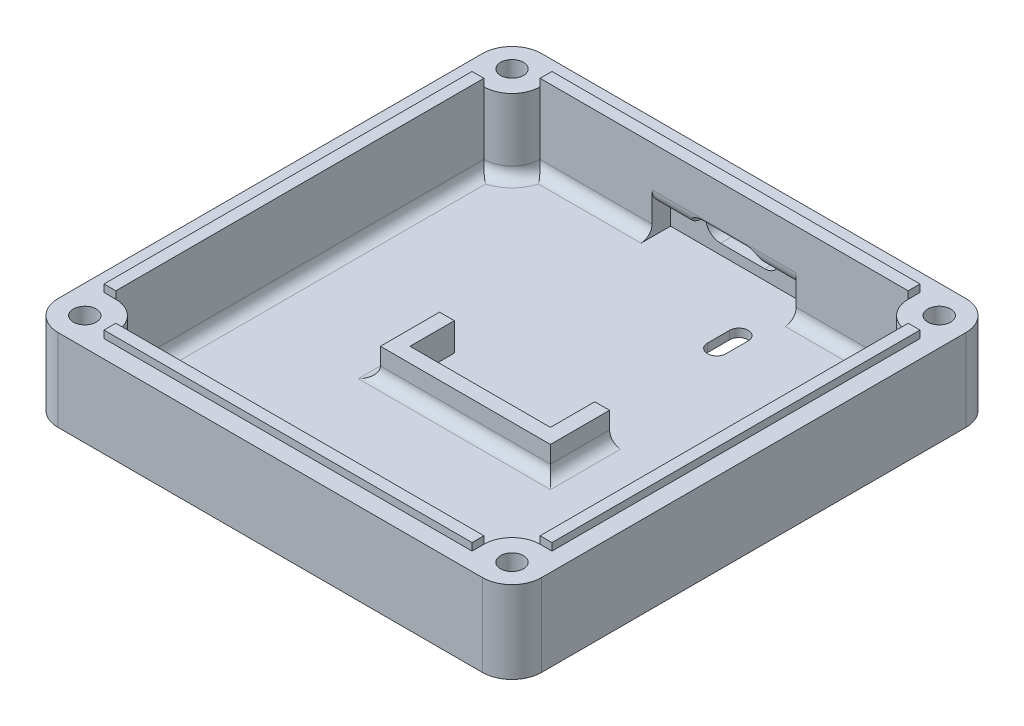
SolidWorks part; units mm, degrees
ref_plane "Front Plane" through (0, 0, 0) normal (0, 0, 1) x (1, 0, 0)
ref_plane "Top Plane" through (0, 0, 0) normal (0, 1, 0) x (1, 0, 0)
ref_plane "Right Plane" through (0, 0, 0) normal (1, 0, 0) x (0, 0, -1)
sketch "Sketch1" plane through (0, 0, 0) normal (0, 1, 0) x (1, 0, 0)
  line L1 (-32.7, -32.7) -> (32.7, -32.7)
  line L2 (-32.7, -32.7) -> (-32.7, 32.7)
  line L3 (-32.7, 32.7) -> (32.7, 32.7)
  line L4 (32.7, -32.7) -> (32.7, 32.7)
  line L5 (-32.7, -32.7) -> (32.7, 32.7) construction
  line L6 (-32.7, 32.7) -> (32.7, -32.7) construction
  point P0 (0, 0)
  dimension "D1" = 65.4
  dimension "D2" = 65.4
extrude "Boss-Extrude1" add sketch "Sketch1" along normal blind 1.12
fillet "Fillet1" radius 4 4 edges at (-32.7, 0.56, -32.7) (32.7, 0.56, -32.7) (32.7, 0.56, 32.7) (-32.7, 0.56, 32.7)
sketch "Sketch2" plane through (0, 1.12, 0) normal (0, 1, 0) x (1, 0, 0)
  line L0 (-32.7, 28.7) -> (-32.7, -28.7)
  line L1 (-28.7, -32.7) -> (28.7, -32.7)
  line L2 (32.7, -28.7) -> (32.7, 28.7)
  line L3 (28.7, 32.7) -> (-28.7, 32.7)
  line L4 (0, 0) -> (0, 28.7) construction
  line L11 (0, 0) -> (28.7, 0) construction
  line L12 (0, 0) -> (-28.7, 0) construction
  line L13 (0, 0) -> (0, -28.7) construction
  line L14 (24.9, 28.7) -> (-24.9, 28.7)
  line L15 (28.7, -24.9) -> (28.7, 24.9)
  line L16 (-24.9, -28.7) -> (24.9, -28.7)
  line L17 (-28.7, -24.9) -> (-28.7, 24.9)
  arc A0 (-32.7, -28.7) -> (-28.7, -32.7) centre (-28.7, -28.7) ccw
  arc A1 (28.7, -32.7) -> (32.7, -28.7) centre (28.7, -28.7) ccw
  arc A2 (32.7, 28.7) -> (28.7, 32.7) centre (28.7, 28.7) ccw
  arc A3 (-28.7, 32.7) -> (-32.7, 28.7) centre (-28.7, 28.7) ccw
  arc A5 (-28.7, 24.9) -> (-24.9, 28.7) centre (-28.7, 28.7) ccw
  arc A6 (24.9, 28.7) -> (28.7, 24.9) centre (28.7, 28.7) ccw
  arc A7 (-28.7, -24.9) -> (-24.9, -28.7) centre (-28.7, -28.7) cw
  arc A8 (28.7, -24.9) -> (24.9, -28.7) centre (28.7, -28.7) ccw
  point P29 (0, 28.7)
  point P32 (28.7, 0)
  point P35 (0, -28.7)
  point P38 (-28.7, 0)
  dimension "D5" = 3.8
  dimension "D6" = 3.8
  dimension "D7" = 3.8
  dimension "D1" = 4
  dimension "D2" = 4
  dimension "D3" = 4
  dimension "D4" = 4
extrude "Boss-Extrude2" add sketch "Sketch2" along normal blind 10
sketch "Sketch3" plane through (0, 0, -32.7) normal (0, 0, -1) x (-1, 0, 0)
  line L0 (0, 0) -> (0, 4.5) construction
  line L1 (-3, 4.5) -> (3, 4.5) construction
  line L2 (-3, 6.5) -> (3, 6.5)
  line L3 (-3, 2.5) -> (3, 2.5)
  arc A0 (-3, 6.5) -> (-3, 2.5) centre (-3, 4.5) ccw
  arc A1 (3, 2.5) -> (3, 6.5) centre (3, 4.5) ccw
  point P5 (0, 4.5)
  point P10 (-5, 4.5)
  point P11 (5, 4.5)
  dimension "D1" = 4.5
  dimension "D2" = 4
  dimension "D3" = 10
extrude "Cut-Extrude1" cut sketch "Sketch3" against normal up to next
sketch "Sketch4" plane through (0, 0, -28.7) normal (0, 0, 1) x (1, 0, 0)
  line L0 (0, 0) -> (0, 4.62) construction
  line L1 (28.7, 0) -> (-28.7, 0) construction
  line L2 (-9.75, 4.62) -> (9.75, 4.62)
  line L3 (-24.9, 1.12) -> (24.9, 1.12) construction
  line L4 (24.9, 1.12) -> (24.9, 11.12) construction
  line L5 (24.9, 11.12) -> (-24.9, 11.12) construction
  line L6 (-24.9, 11.12) -> (-24.9, 1.12) construction
  line L7 (-28.7, 0) -> (-28.7, 11.12) construction
  line L8 (-28.7, 11.12) -> (28.7, 11.12) construction
  line L9 (28.7, 11.12) -> (28.7, 0) construction
  line L10 (-24.9, 1.12) -> (24.9, 1.12)
  line L11 (24.9, 1.12) -> (24.9, 11.12)
  line L12 (24.9, 11.12) -> (-24.9, 11.12)
  line L13 (-24.9, 11.12) -> (-24.9, 1.12)
  line L14 (28.7, 0) -> (-28.7, 0)
  line L15 (-28.7, 0) -> (-28.7, 11.12)
  line L16 (-28.7, 11.12) -> (28.7, 11.12)
  line L17 (28.7, 11.12) -> (28.7, 0)
  line L18 (-9.75, 4.62) -> (-9.75, 1.12)
  line L19 (-9.75, 1.12) -> (9.75, 1.12)
  line L20 (9.75, 1.12) -> (9.75, 4.62)
  point P7 (0, 4.62)
  dimension "D1" = 19.5
  dimension "D2" = 3.5
extrude "Cut-Extrude2" cut sketch "Sketch4" against normal blind 2.5 contours L2 L20 L19 L18
fillet "Fillet3" radius 2 2 edges at (7.3732, 4.62, -28.7) (-7.3732, 4.62, -28.7)
sketch "Sketch5" plane through (0, 11.12, 0) normal (0, 1, 0) x (1, 0, 0)
  line L0 (-28.7, 0) -> (28.7, 0) construction
  line L1 (28.7, -24.9) -> (28.7, 24.9) construction
  line L2 (0, -28.7) -> (0, 28.7) construction
  line L3 (24.9, 28.7) -> (-24.9, 28.7) construction
  line L4 (-28.7, -24.9) -> (-28.7, 24.9)
  line L5 (-28.7, 24.9) -> (-30.3, 24.9)
  line L6 (-30.3, 24.9) -> (-30.3, -24.9)
  line L7 (-30.3, -24.9) -> (-28.7, -24.9)
  line L8 (24.9, -28.7) -> (-24.9, -28.7)
  line L9 (-24.9, -28.7) -> (-24.9, -30.3)
  line L10 (-24.9, -30.3) -> (24.9, -30.3)
  line L11 (24.9, -30.3) -> (24.9, -28.7)
  line L12 (28.7, 24.9) -> (28.7, -24.9)
  line L13 (28.7, -24.9) -> (30.3, -24.9)
  line L14 (30.3, -24.9) -> (30.3, 24.9)
  line L15 (30.3, 24.9) -> (28.7, 24.9)
  line L16 (24.9, 28.7) -> (-24.9, 28.7)
  line L17 (-24.9, 28.7) -> (-24.9, 30.3)
  line L18 (-24.9, 30.3) -> (24.9, 30.3)
  line L19 (24.9, 30.3) -> (24.9, 28.7)
  point P6 (0, 0)
  point P12 (0, 0)
  point P16 (-28.7, 0)
  point P22 (0, -28.7)
  point P28 (28.7, 0)
  point P34 (0, 28.7)
  dimension "D1" = 1.6
  dimension "D2" = 1.6
  dimension "D3" = 1.6
  dimension "D4" = 1.6
extrude "Boss-Extrude3" add sketch "Sketch5" along normal blind 1
sketch "Sketch6" plane through (0, 1.12, 0) normal (0, 1, 0) x (1, 0, 0)
  line L0 (0, 31.2) -> (0, -4.3) construction
  line L1 (-9.5, -4.3) -> (9.5, -4.3)
  line L2 (-9.5, -4.3) -> (-9.5, 1.7)
  line L3 (-9.5, 1.7) -> (-11.5, 1.7)
  line L4 (-11.5, 1.7) -> (-11.5, -6.3)
  line L5 (-11.5, -6.3) -> (11.5, -6.3)
  line L6 (11.5, -6.3) -> (11.5, 1.7)
  line L7 (11.5, 1.7) -> (9.5, 1.7)
  line L8 (28.7, -24.9) -> (28.7, 24.9)
  line L9 (24.9, 28.7) -> (9.75, 28.7)
  line L10 (9.75, 28.7) -> (9.75, 31.2)
  line L11 (9.75, 31.2) -> (-9.75, 31.2)
  line L12 (-9.75, 31.2) -> (-9.75, 28.7)
  line L13 (-9.75, 28.7) -> (-24.9, 28.7)
  line L14 (-28.7, 24.9) -> (-28.7, -24.9)
  line L15 (-24.9, -28.7) -> (24.9, -28.7)
  line L16 (28.7, -24.9) -> (28.7, 24.9)
  line L17 (24.9, 28.7) -> (9.75, 28.7)
  line L18 (9.75, 28.7) -> (9.75, 31.2)
  line L19 (9.75, 31.2) -> (-9.75, 31.2)
  line L20 (-9.75, 31.2) -> (-9.75, 28.7)
  line L21 (-9.75, 28.7) -> (-24.9, 28.7)
  line L22 (-28.7, 24.9) -> (-28.7, -24.9)
  line L23 (-24.9, -28.7) -> (24.9, -28.7)
  line L24 (9.5, 1.7) -> (9.5, -4.3)
  arc A4 (24.9, 28.7) -> (28.7, 24.9) centre (28.7, 28.7) ccw
  arc A5 (-28.7, 24.9) -> (-24.9, 28.7) centre (-28.7, 28.7) ccw
  arc A6 (-24.9, -28.7) -> (-28.7, -24.9) centre (-28.7, -28.7) ccw
  arc A7 (28.7, -24.9) -> (24.9, -28.7) centre (28.7, -28.7) ccw
  arc A8 (24.9, 28.7) -> (28.7, 24.9) centre (28.7, 28.7) ccw
  arc A9 (-28.7, 24.9) -> (-24.9, 28.7) centre (-28.7, 28.7) ccw
  arc A10 (-24.9, -28.7) -> (-28.7, -24.9) centre (-28.7, -28.7) ccw
  arc A11 (28.7, -24.9) -> (24.9, -28.7) centre (28.7, -28.7) ccw
  point P18 (0, -4.3)
  dimension "D2" = 19
  dimension "D3" = 35.5
  dimension "D4" = 2
  dimension "D5" = 2
  dimension "D6" = 2
  dimension "D7" = 6
  dimension "D8" = 6
  dimension "D1" = 0
extrude "Boss-Extrude4" add sketch "Sketch6" along normal blind 3.8 contours L24 L1 L2 L3 L4 L5 L6 L7
sketch "Sketch7" plane through (0, 11.12, 0) normal (0, 1, 0) x (1, 0, 0)
  line L1 (-28.9, -28.9) -> (28.9, -28.9) construction
  line L2 (-28.9, -28.9) -> (-28.9, 28.9) construction
  line L3 (-28.9, 28.9) -> (28.9, 28.9) construction
  line L4 (28.9, -28.9) -> (28.9, 28.9) construction
  line L5 (-28.9, -28.9) -> (28.9, 28.9) construction
  line L6 (-28.9, 28.9) -> (28.9, -28.9) construction
  circle A0 centre (-28.9, 28.9) radius 1.55
  circle A1 centre (28.9, 28.9) radius 1.55
  circle A2 centre (28.9, -28.9) radius 1.55
  circle A3 centre (-28.9, -28.9) radius 1.55
  point P0 (0, 0)
  dimension "D3" = 3.1
  dimension "D4" = 3.1
  dimension "D5" = 3.1
  dimension "D6" = 3.1
  dimension "D1" = 57.8
  dimension "D2" = 57.8
extrude "Cut-Extrude3" cut sketch "Sketch7" against normal up to surface (11.12 mm away) up to face at (0, 0, 0)
sketch "Sketch8" plane through (0, 0, 0) normal (0, -1, 0) x (1, 0, 0)
  circle A0 centre (-28.9, 28.9) radius 2.75
  circle A1 centre (28.9, 28.9) radius 2.75
  circle A2 centre (28.9, -28.9) radius 2.75
  circle A3 centre (-28.9, -28.9) radius 2.75
  dimension "D1" = 5.5
  dimension "D2" = 5.5
  dimension "D3" = 5.5
  dimension "D4" = 5.5
extrude "Cut-Extrude4" cut sketch "Sketch8" against normal blind 4
fillet "Fillet4" radius 1.5 3 edges at (11.5, 1.12, 2.3) (-11.5, 1.12, 2.3) (0, 1.12, 6.3)
fillet "Fillet5" radius 1.5 9 edges at (-26.013, 1.12, 26.013) (26.013, 1.12, 26.013) (26.013, 1.12, -26.013) (-26.013, 1.12, -26.013) (0, 1.12, 28.7) (28.7, 1.12, 0) (17.325, 1.12, -28.7) (-17.325, 1.12, -28.7) (-28.7, 1.12, 0)
sketch "Sketch9" plane through (0, 0, 0) normal (0, -1, 0) x (1, 0, 0)
  line L0 (32.7, -21.5) -> (7.7, -21.5) construction
  line L1 (32.7, 28.7) -> (32.7, -28.7) construction
  line L2 (7.7, -21.5) -> (7.7, -32.7) construction
  line L3 (28.7, -32.7) -> (-28.7, -32.7) construction
  line L4 (7.7, -23) -> (7.7, -20) construction
  line L5 (6.45, -23) -> (6.45, -20)
  line L6 (8.95, -23) -> (8.95, -20)
  line L7 (7.7, -20) -> (7.7, 32.7) construction
  line L8 (-28.7, 32.7) -> (28.7, 32.7) construction
  arc A0 (6.45, -23) -> (8.95, -23) centre (7.7, -23) ccw
  arc A1 (8.95, -20) -> (6.45, -20) centre (7.7, -20) ccw
  point P10 (7.7, -21.5)
  point P19 (7.7, -24.25)
  point P20 (7.7, -18.75)
  dimension "D4" = 5.5
  dimension "D1" = 25
  dimension "D2" = 11.2
  dimension "D3" = 2.5
extrude "Cut-Extrude5" cut sketch "Sketch9" against normal up to next
